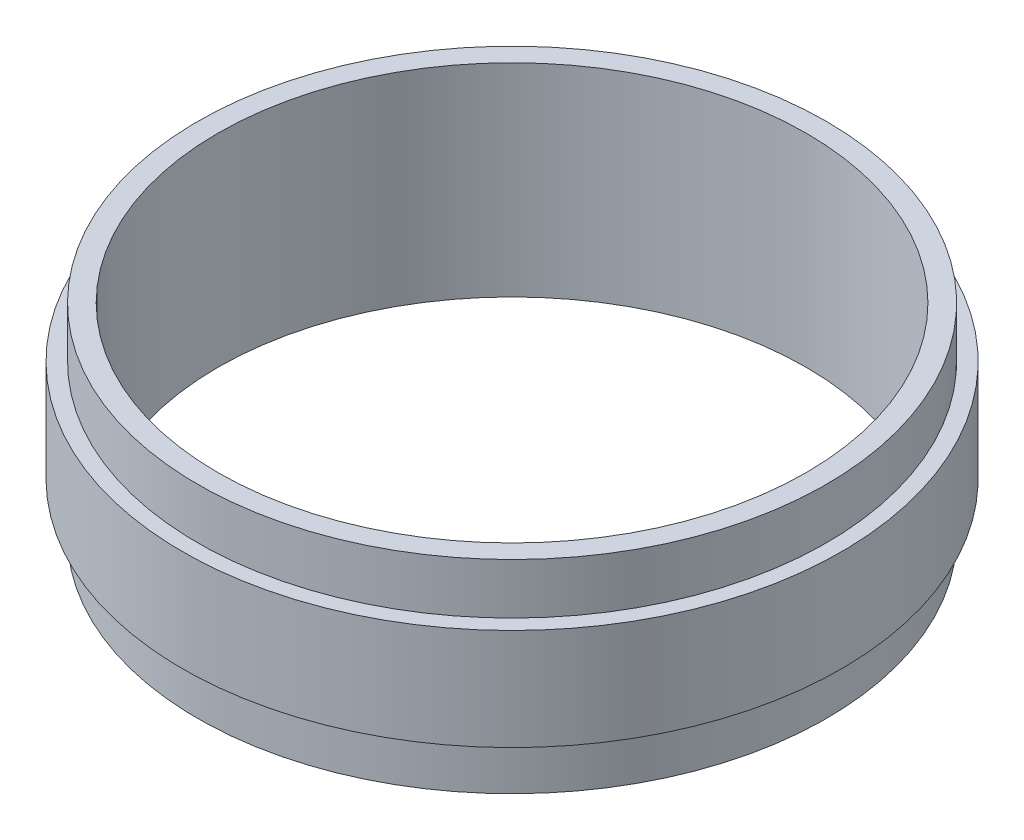
SolidWorks part; units mm, degrees
material "HYPALON"
ref_plane "Front Plane" through (0, 0, 0) normal (0, 0, 1) x (1, 0, 0)
ref_plane "Top Plane" through (0, 0, 0) normal (0, 1, 0) x (1, 0, 0)
ref_plane "Right Plane" through (0, 0, 0) normal (1, 0, 0) x (0, 0, -1)
sketch "Szkic1" plane through (0, 0, 0) normal (0, 0, 1) x (1, 0, 0)
  line L0 (0, 0) -> (-65, 0)
  line L1 (-65, 10) -> (-62, 10)
  line L3 (-58, 0) -> (-58, 40)
  line L4 (-62, 10) -> (-62, 0)
  line L5 (-58, 40) -> (-62, 40)
  line L7 (-65, 10) -> (-65, 30)
  line L8 (-65, 30) -> (-62, 30)
  line L9 (-62, 30) -> (-62, 40)
  line L13 (0, 0) -> (0, 22.4148)
  point P3 (-65, 5.6285)
  point P7 (-65, 0)
  point P8 (0, 0)
  dimension "D1" = 65
  dimension "D2" = 10
  dimension "D3" = 7
  dimension "D4" = 40
  dimension "D5" = 3
  dimension "D7" = 3
  dimension "D8" = 10
revolve "Obrót1" add sketch "Szkic1" angle 360 about L13 region at (-60.9545, 20, 0)
